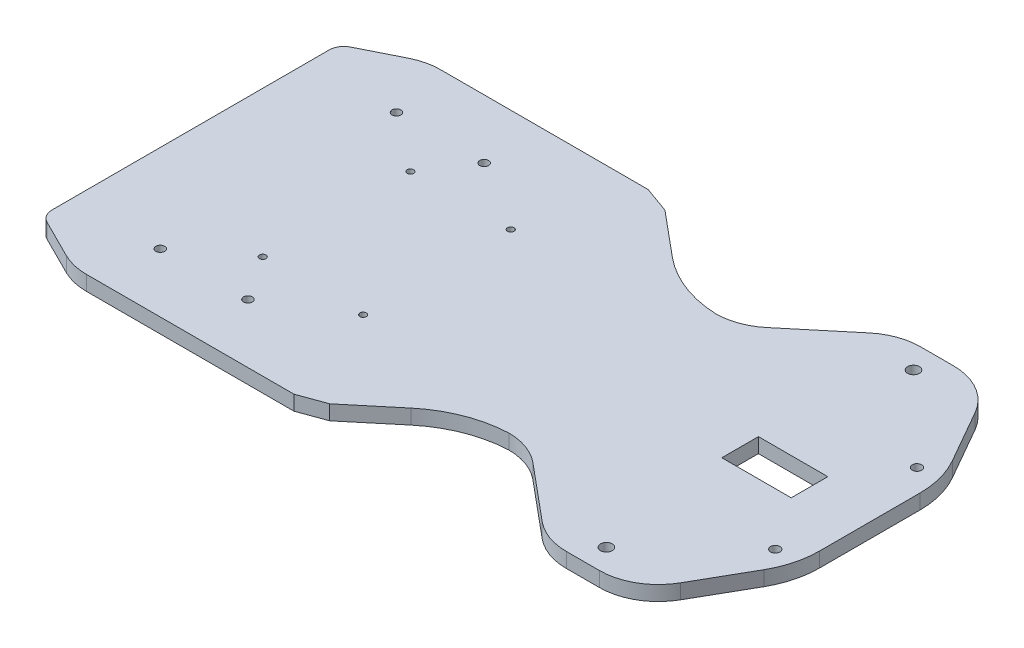
SolidWorks part; units mm, degrees
ref_plane "Front Plane" through (0, 0, 0) normal (0, 0, 1) x (1, 0, 0)
ref_plane "Top Plane" through (0, 0, 0) normal (0, 1, 0) x (1, 0, 0)
ref_plane "Right Plane" through (0, 0, 0) normal (1, 0, 0) x (0, 0, -1)
sketch "Sketch1" plane through (0, 0, 0) normal (0, 1, 0) x (1, 0, 0)
  line L0 (40, 60) -> (70, 60)
  line L1 (70, 60) -> (90, 25)
  line L2 (90, 25) -> (90, -25)
  line L3 (90, -25) -> (70, -60)
  line L4 (70, -60) -> (40, -60)
  line L5 (40, 60) -> (10, 35)
  line L6 (10, 35) -> (-10, 35)
  line L7 (-10, 35) -> (-40, 60)
  line L8 (-40, 60) -> (-120, 60)
  line L9 (-120, 60) -> (-140, 50)
  line L10 (-140, 50) -> (-140, -50)
  line L11 (-140, -50) -> (-120, -60)
  line L12 (-120, -60) -> (-40, -60)
  line L13 (-40, -60) -> (-10, -35)
  line L14 (-10, -35) -> (10, -35)
  line L15 (10, -35) -> (40, -60)
  point P31 (90, 0)
  point P33 (0, 35)
  point P35 (-140, 0)
  dimension "D1" = 120
  dimension "D2" = 70
  dimension "D3" = 20
  dimension "D4" = 30
  dimension "D5" = 20
  dimension "D6" = 100
  dimension "D7" = 100
  dimension "D8" = 20
  dimension "D9" = 30
  dimension "D10" = 50
extrude "Boss-Extrude1" add sketch "Sketch1" along normal blind 5
chamfer "Chamfer1" distance 5 angle 20 2 edges at (-40, 2.5, -60) (-40, 2.5, 60) first distance on face at (-25, 2.5, -47.5) first distance on face at (-80, 2.5, 60)
fillet "Fillet4" radius 20 4 edges at (40, 2.5, -60) (40, 2.5, 60) (70, 2.5, -60) (70, 2.5, 60)
sketch "Sketch3" plane through (0, 5, 0) normal (0, 1, 0) x (1, 0, 0)
  line L0 (58.3935, 60) -> (47.241, 60) construction
  line L1 (47.241, -60) -> (58.3935, -60) construction
  point P0 (52.8173, 52)
  point P1 (52.8173, -52)
  point P5 (52.8173, 60)
  dimension "D1" = 8
  dimension "D2" = 8
hole_wizard "Ø4.0mm Dowel Hole1" positions "3DSketch1" profile "Sketch4" hole size "Ø4.0" standard "ANSI Metric" end condition through all
sketch3d "3DSketch1"
  point P0 (52.8173, 5, -52)
  point P3 (52.8173, 5, 52)
sketch "Sketch4" plane through (52.8173, 5, -52) normal (1, 0, 0) x (0, 0, 1)
  line L0 (0, 0) -> (0, 5)
  line L1 (0, 5) -> (2, 5)
  line L2 (2, 5) -> (2, 0)
  line L5 (2, 0) -> (0, 0)
  line L11 (0, -6.35) -> (0, 107.95) construction
  dimension "Thru Hole Dia." = 4
  dimension "Thru Hole Depth" = 5
sketch "Sketch5" plane through (0, 0, 0) normal (0, -1, 0) x (1, 0, 0)
  circle A0 centre (52.8173, 52) radius 2.75
  circle A1 centre (52.8173, -52) radius 2.75
  dimension "D1" = 5.5
  dimension "D2" = 5.5
extrude "Cut-Extrude1" cut sketch "Sketch5" against normal blind 2
fillet "Fillet5" radius 30 2 edges at (90, 2.5, 25) (90, 2.5, -25)
fillet "Fillet6" radius 20 2 edges at (10, 2.5, -35) (10, 2.5, 35)
fillet "Fillet7" radius 40 2 edges at (-10, 2.5, -35) (-10, 2.5, 35)
fillet "Fillet8" radius 20 2 edges at (-120, 2.5, 60) (-120, 2.5, -60)
fillet "Fillet9" radius 5 2 edges at (-140, 2.5, 50) (-140, 2.5, -50)
sketch "Sketch7" plane through (0, 5, 0) normal (0, 1, 0) x (1, 0, 0)
  line L0 (-45.0471, 60) -> (-115.2786, 60) construction
  circle A0 centre (-110.2786, 40) radius 1.5
  circle A1 centre (-80.5786, 40) radius 1.5
  dimension "D1" = 5
  dimension "D2" = 3
  dimension "D3" = 29.7
  dimension "D4" = 20
extrude "Cut-Extrude3" cut sketch "Sketch7" against normal up to next
mirror "Mirror1" about plane through (0, 0, 0) normal (0, 0, 1) of "Cut-Extrude3"
sketch "Sketch8" plane through (0, 5, 0) normal (0, 1, 0) x (1, 0, 0)
  line L0 (58.3935, 60) -> (47.241, 60) construction
  line L1 (46.1, 6.2) -> (69.6, 6.2)
  line L2 (46.1, 6.2) -> (46.1, -6.2)
  line L3 (46.1, -6.2) -> (69.6, -6.2)
  line L4 (69.6, 6.2) -> (69.6, -6.2)
  line L5 (90, -17.0331) -> (90, 17.0331) construction
  point P8 (69.6, 0)
  point P9 (90, 0)
  dimension "D1" = 53.8
  dimension "D2" = 23.5
  dimension "D3" = 20.4
extrude "Cut-Extrude4" cut sketch "Sketch8" against normal up to next
sketch "Sketch9" plane through (0, 5, 0) normal (0, 1, 0) x (1, 0, 0)
  line L0 (-45.0471, 60) -> (-115.2786, 60) construction
  circle A0 centre (-90.5786, 25) radius 1.1
  circle A1 centre (-56.5786, 25) radius 1.1
  circle A2 centre (-90.5786, -25) radius 1.1
  circle A3 centre (-56.5786, -25) radius 1.1
  circle A5 centre (-80.5786, 40) radius 1.5 construction
  dimension "D1" = 2.2
  dimension "D5" = 10
  dimension "D2" = 34
  dimension "D3" = 50
  dimension "D4" = 35
extrude "Cut-Extrude5" cut sketch "Sketch9" against normal up to next
sketch "Sketch11" plane through (0, 5, 0) normal (0, 1, 0) x (1, 0, 0)
  line L0 (90, -17.0331) -> (90, 17.0331) construction
  line L1 (82, 24) -> (82, -24) construction
  circle A0 centre (82, 24) radius 1.6
  circle A1 centre (82, -24) radius 1.6
  point P4 (82, 0)
  point P7 (90, 0)
  dimension "D1" = 3.2
  dimension "D2" = 8
  dimension "D3" = 48
extrude "Cut-Extrude6" cut sketch "Sketch11" against normal up to next
